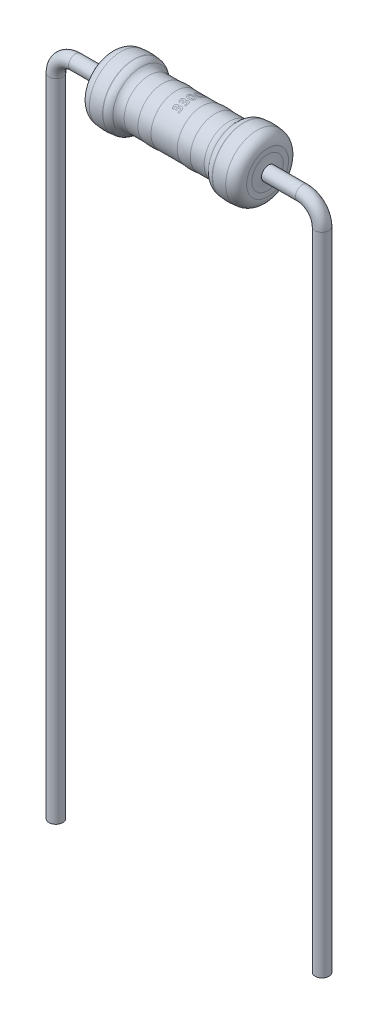
SolidWorks part; units mm, degrees
material "Plain Carbon Steel"
ref_plane "Front Plane" through (0, 0, 0) normal (0, 0, 1) x (1, 0, 0)
ref_plane "Top Plane" through (0, 0, 0) normal (0, 1, 0) x (1, 0, 0)
ref_plane "Right Plane" through (0, 0, 0) normal (1, 0, 0) x (0, 0, -1)
sketch "Sketch1" plane through (0, 0, 0) normal (0, 0, 1) x (1, 0, 0)
  line L0 (-4.33, 0) -> (4.33, 0)
  line L1 (-5.08, -0.75) -> (-5.08, -25.4)
  line L2 (5.08, -0.75) -> (5.08, -25.4)
  line L3 (-5.08, -25.4) -> (5.08, -25.4) construction
  line L4 (0, 0) -> (0, -25.4) construction
  arc A0 (-4.33, 0) -> (-5.08, -0.75) centre (-4.33, -0.75) ccw
  arc A1 (4.33, 0) -> (5.08, -0.75) centre (4.33, -0.75) cw
  dimension "D2" = 0.75
  dimension "D1" = 10.16
  dimension "D3" = 25.4
ref_plane "Plane1" through (-5.08, -25.4, 0) normal (0, -1, 0) x (-1, 0, 0)
sketch "Sketch2" plane through (-5.08, -25.4, 0) normal (0, -1, 0) x (-1, 0, 0)
  circle A0 centre (0, 0) radius 0.265
  dimension "D1" = 0.53
sweep "Sweep1" add profiles "Sketch2" path "Sketch1"
sketch "Sketch3" plane through (0, 0, 0) normal (0, 0, 1) x (1, 0, 0)
  line L0 (-3, 0) -> (3, 0)
  line L5 (-3, 0) -> (-3, 1.2)
  line L6 (3, 0) -> (3, 1.2)
  line L7 (-3, 1.2) -> (-1.75, 1.2)
  line L8 (3, 1.2) -> (1.75, 1.2)
  line L9 (-1.75, 1.2) -> (-1.75, 0.95)
  line L10 (-1.75, 0.95) -> (1.75, 0.95)
  line L11 (1.75, 0.95) -> (1.75, 1.2)
  line L12 (0, 0) -> (0, 0.95) construction
  dimension "D1" = 6
  dimension "D2" = 1.2
  dimension "D3" = 3.5
  dimension "D4" = 0.95
  dimension "D5" = 0.25
revolve "Revolve1" add sketch "Sketch3" angle 360 about L0
fillet "Fillet-1" radius 0.35 2 edges at (1.75, 0, 1.2) (-1.75, 0, 1.2)
fillet "Fillet-2" radius 0.4 4 edges at (3, 0, 1.2) (-3, 0, 1.2) (1.75, 0, 0.95) (-1.75, 0, 0.95)
sketch "Sketch5" plane through (0, 0, 0) normal (0, 0, 1) x (1, 0, 0)
  line L16 (-3, 0) -> (3, 0) construction
  line L17 (-2.6, 1.2) -> (-2.1, 1.2) construction
  line L18 (-2.6, 1.2) -> (-2.6, 0)
  line L19 (-2.6, 0) -> (-2.1, 0)
  line L20 (-2.1, 1.2) -> (-2.1, 0)
  line L21 (-1.75, 0.95) -> (1.75, 0.95) construction
  line L22 (2.6, 1.2) -> (2.1, 1.2) construction
  line L23 (2.6, 1.2) -> (2.6, 0)
  line L24 (2.6, 0) -> (2.1, 0)
  line L25 (2.1, 1.2) -> (2.1, 0)
  line L26 (-0.5, 0.95) -> (-1, 0.95) construction
  line L27 (-0.5, 0.95) -> (-0.5, 0)
  line L28 (-0.5, 0) -> (-1, 0)
  line L29 (-1, 0.95) -> (-1, 0)
  line L30 (-2.35, 1.2) -> (-2.35, 1.22) construction
  line L31 (1, 0.95) -> (0.5, 0.95) construction
  line L32 (1, 0.95) -> (1, 0)
  line L33 (1, 0) -> (0.5, 0)
  line L34 (0.5, 0.95) -> (0.5, 0)
  line L35 (-0.75, 0.95) -> (-0.75, 0.97) construction
  line L36 (0.75, 0.95) -> (0.75, 0.97) construction
  line L37 (2.35, 1.2) -> (2.35, 1.22) construction
  line L48 (-3, 0) -> (-3, 0.6)
  line L49 (-3, 0) -> (-3, 1.2) construction
  line L50 (-3, 0) -> (-3.05, 0)
  line L51 (-3.05, 0) -> (-3.05, 0.2)
  line L52 (3, 0) -> (3.05, 0)
  line L53 (3.05, 0) -> (3.05, 0.2)
  line L54 (3, 0) -> (3, 0.6)
  line L55 (3, 0) -> (3, 1.2) construction
  arc A0 (-2.6, 1.2) -> (-2.1, 1.2) centre (-2.35, -0.3525) cw
  arc A1 (-1, 0.95) -> (-0.5, 0.95) centre (-0.75, -0.6025) cw
  arc A2 (0.5, 0.95) -> (1, 0.95) centre (0.75, -0.6025) cw
  arc A3 (2.1, 1.2) -> (2.6, 1.2) centre (2.35, -0.3525) cw
  arc A6 (-3, 0.6) -> (-3.05, 0.2) centre (-4.625, 0.6) cw
  arc A7 (3.05, 0.2) -> (3, 0.6) centre (4.625, 0.6) cw
  dimension "D4" = 0.02
  dimension "D5" = 0.05
  dimension "D7" = 0.6
  dimension "D1" = 0.5
  dimension "D2" = 0.5
  dimension "D3" = 0.5
  dimension "D6" = 0.2
revolve "Revolve3" add sketch "Sketch5" angle 360 about L19
ref_plane "Plane2" through (0, 2, 0) normal (0, 1, 0) x (1, 0, 0)
sketch "Sketch6" plane through (0, 2, 0) normal (0, 1, 0) x (1, 0, 0)
  line L0 (0, 0) -> (0.15, 0) construction
  line L1 (0.15, 0.95) -> (0.15, -0.95) construction
  line L2 (0.5, 0.95) -> (-0.5, 0.95) construction
  text T0 "330Ω" font "Calibri" height 0.3
  dimension "D1" = 0.15
wrap "Wrap1" sketch "Sketch6" wrap type scribe source sketch "Sketch6" face at (-0.5, -0.95, 0)
